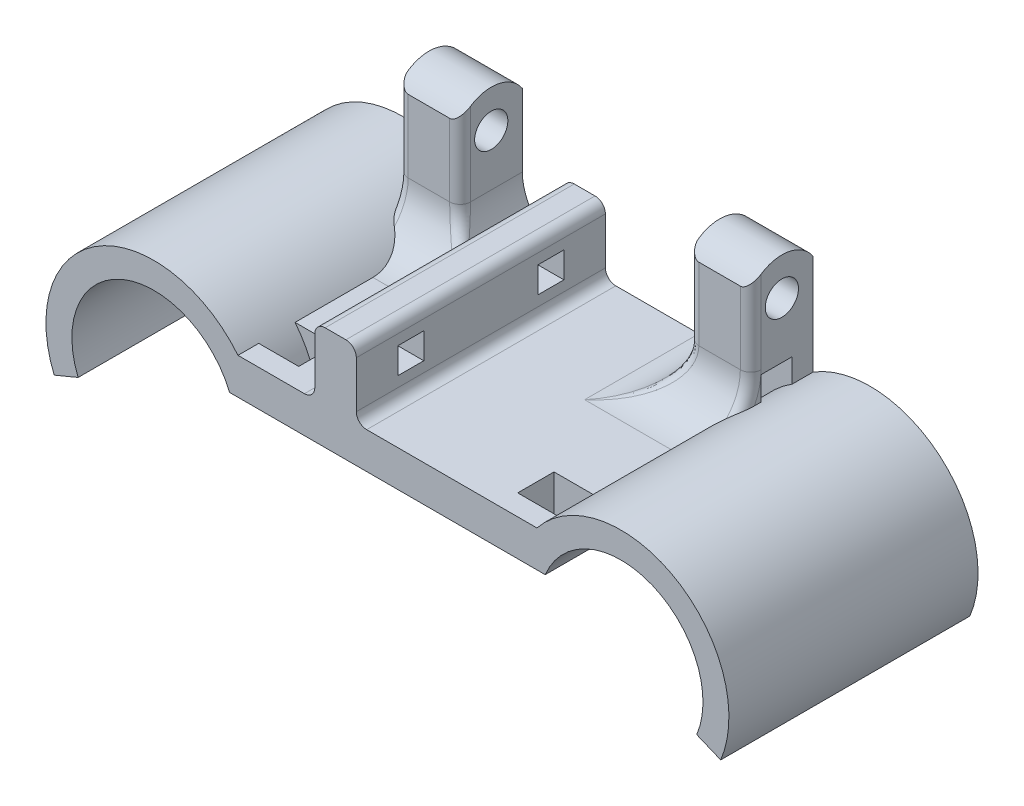
SolidWorks part; units mm, degrees
ref_plane "Front" through (0, 0, 0) normal (0, 0, 1) x (1, 0, 0)
ref_plane "Top" through (0, 0, 0) normal (0, 1, 0) x (1, 0, 0)
ref_plane "Right" through (0, 0, 0) normal (1, 0, 0) x (0, 0, -1)
sketch "Sketch1" plane through (0, 0, 0) normal (0, 0, 1) x (1, 0, 0)
  line L0 (-29.7986, -6.0464) -> (-22.5, -3.0232) construction
  line L1 (-22.5, -3.0232) -> (-15.2014, 0) construction
  line L2 (-22.5, -3.0232) -> (-22.5, 4.8768) construction
  arc A0 (-15.2014, 0) -> (-29.7986, -6.0464) centre (-22.5, -3.0232) ccw
  dimension "D2" = 7.9
  dimension "D1" = 22.5
  dimension "D3" = 180
  dimension "D4" = 67.5
extrude "Extrude-LM8UU Cup" add sketch "Sketch1" along normal blind 24 thin thin type one direction wall 2.5
sketch "Sketch2" plane through (0, 0, 0) normal (0, 0, 1) x (1, 0, 0)
  line L0 (0, 0) -> (-15.2014, 0)
extrude "Extrude-Straight" add sketch "Sketch2" along normal through all thin thin type one direction wall 3.5
sketch "Sketch5" plane through (0, 0, 24) normal (0, 0, 1) x (1, 0, 0)
  line L0 (0, 0) -> (-15.2014, 0) construction
  line L1 (-12.5491, 0) -> (-10.5491, 0)
  line L2 (-10.5491, 0) -> (-10.5491, 3.5)
  line L3 (0, 3.5) -> (-14.4001, 3.5) construction
  line L4 (-10.5491, 3.5) -> (-14.4001, 3.5)
  arc A0 (-14.4001, 3.5) -> (-12.5491, 0) centre (-22.5, -3.0232) cw
  arc A1 (-14.4001, 3.5) -> (-32.1083, -7.0031) centre (-22.5, -3.0232) ccw construction
  dimension "D1" = 2
extrude "Cut-Upper Zip Tie" cut sketch "Sketch5" against normal blind 3.5 from offset 2 offset against normal yes
mirror "Mirror-Cup And Straight" about plane through (0, 0, 0) normal (1, 0, 0) of "Extrude-LM8UU Cup", "Extrude-Straight", "Cut-Upper Zip Tie"
sketch "Sketch6" plane through (0, 0, 0) normal (1, 0, 0) x (0, 0, -1)
  line L1 (-6, 3.5) -> (0, 3.5)
  line L2 (-6, 3.5) -> (-6, 15.4768)
  line L3 (-6, 15.4768) -> (0, 15.4768)
  line L4 (0, 3.5) -> (0, 15.4768)
  dimension "D1" = 6
  dimension "D2" = 18.5
extrude "Boss-Rod Attachments" add sketch "Sketch6" along normal blind 6 from offset 11
sketch "Sketch7" plane through (11, 0, 0) normal (-1, 0, 0) x (0, 0, 1)
  line L0 (3, 15.4768) -> (3, 13.4768) construction
  line L1 (0, 15.4768) -> (6, 15.4768) construction
  circle A0 centre (3, 13.4768) radius 1.6
  dimension "D2" = 3.2
  dimension "D1" = 16.5
extrude "Cut-Rod Screw Hole" cut sketch "Sketch7" against normal through all
sketch "Sketch8" plane through (11, 0, 0) normal (-1, 0, 0) x (0, 0, 1)
  line L0 (0, 15.4768) -> (6, 15.4768)
  arc A0 (0, 15.4768) -> (6, 15.4768) centre (3, 13.4768) cw
  circle A1 centre (3, 13.4768) radius 1.6 construction
extrude "Boss-Rod Round End" add sketch "Sketch8" against normal up to surface (6 mm away) up to face at (17, 13.4768, 4.6)
mirror "Mirror-Rod Attachment" about plane through (0, 0, 0) normal (1, 0, 0) of "Boss-Rod Round End", "Cut-Rod Screw Hole", "Boss-Rod Attachments"
fillet "Fillet1" radius 5 4 edges at (12.7001, 3.5, 6) (-12.7001, 3.5, 6) (-11, 3.5, 3) (11, 3.5, 3)
fillet "Fillet2" radius 1 8 edges at (9.5355, 4.9645, 7.4645) (-9.5355, 4.9645, 7.4645) (11, 11.9884, 6) (-11, 11.9884, 6) (17, 7.0951, 6.2014) (-17, 11.9884, 6) (17, 11.9884, 6) (-17, 7.0951, 6.2014)
sketch "Sketch9" plane through (0, 0, 0) normal (1, 0, 0) x (0, 0, -1)
  line L1 (0, 0) -> (-24, 0)
  line L2 (0, 0) -> (0, 10)
  line L3 (0, 10) -> (-24, 10)
  line L4 (-24, 0) -> (-24, 10)
  dimension "D1" = 10
extrude "Boss-Spectra Mount" add sketch "Sketch9" against normal blind 4 from offset 3 offset against normal yes
sketch "Sketch10" plane through (-7, 0, 0) normal (-1, 0, 0) x (0, 0, 1)
  line L1 (17.5, 8) -> (20, 8)
  line L2 (17.5, 8) -> (17.5, 5.5)
  line L3 (17.5, 5.5) -> (20, 5.5)
  line L4 (20, 8) -> (20, 5.5)
  line L5 (24, 10) -> (24, 3.5) construction
  line L6 (11, 3.5) -> (24, 3.5) construction
  dimension "D1" = 2.5
  dimension "D2" = 2
  dimension "D3" = 4
extrude "Cut-Spectra Hole" cut sketch "Sketch10" against normal up to surface (4 mm away) up to face at (-3, 6.75, 12)
pattern_linear "LPattern-Spectra Holes" count 1 spacing 4 along (0, 1, 0) count 2 spacing 13.5 along (0, 0, -1) of "Cut-Spectra Hole"
fillet "Fillet3" radius 1 7 edges at (-7, 3.601, 4.9) (-7, 3.5175, 10.5819) (-7, 3.5, 17.5) (-3, 3.5, 12) (-3, 10, 12) (-7, 10, 12)
sketch "Sketch11" plane through (0, 0, 0) normal (0, 0, -1) x (-1, 0, 0)
  line L0 (-17, 5.8035) -> (-17, 15.4768) construction
  line L1 (-15.2014, 0) -> (15.2014, 0) construction
  line L2 (-17, 8.0903) -> (-21.7583, 7.3503)
  line L3 (-12.5491, 0) -> (-10.4742, 0)
  arc A0 (-12.5491, 0) -> (-14.4001, 3.5) centre (-22.5, -3.0232) ccw construction
  arc A1 (-12.5491, 0) -> (-21.7583, 7.3503) centre (-22.5, -3.0232) ccw
  arc A2 (-10.4742, 0) -> (-17, 8.0903) centre (-22.5, -3.0232) ccw
  arc A3 (-10.6355, 0.5814) -> (-21.6157, 9.3452) centre (-22.5, -3.0232) ccw construction
  arc A4 (-17, 5.8035) -> (-32.1083, -7.0031) centre (-22.5, -3.0232) ccw construction
  dimension "D1" = 2
extrude "Cut-Lower Zip Tie" cut sketch "Sketch11" against normal blind 3 from offset 2 offset against normal yes
mirror "Mirror-Lower Zip Tie" about plane through (0, 0, 0) normal (1, 0, 0) of "Cut-Lower Zip Tie"
sketch "Sketch13" plane through (0, 0, 0) normal (0, 0, -1) x (-1, 0, 0)
  circle A0 centre (0, 13) radius 3.5
  dimension "D1" = 7
  dimension "D2" = 13
extrude "Boss-Magnet Boss" [suppressed] add sketch "Sketch13" against normal blind 3.5
sketch "Sketch12" [suppressed] plane through (0, 0, 0) normal (0, 0, -1) x (-1, 0, 0)
  circle A0 centre (0, 13) radius 2.5
  arc A1 (2.8723, 15) -> (0, 9.5) centre (0, 13) ccw construction
  dimension "D1" = 5
extrude "Cut-Magnet Slot" [suppressed] cut sketch "Sketch12" against normal blind 2.5
